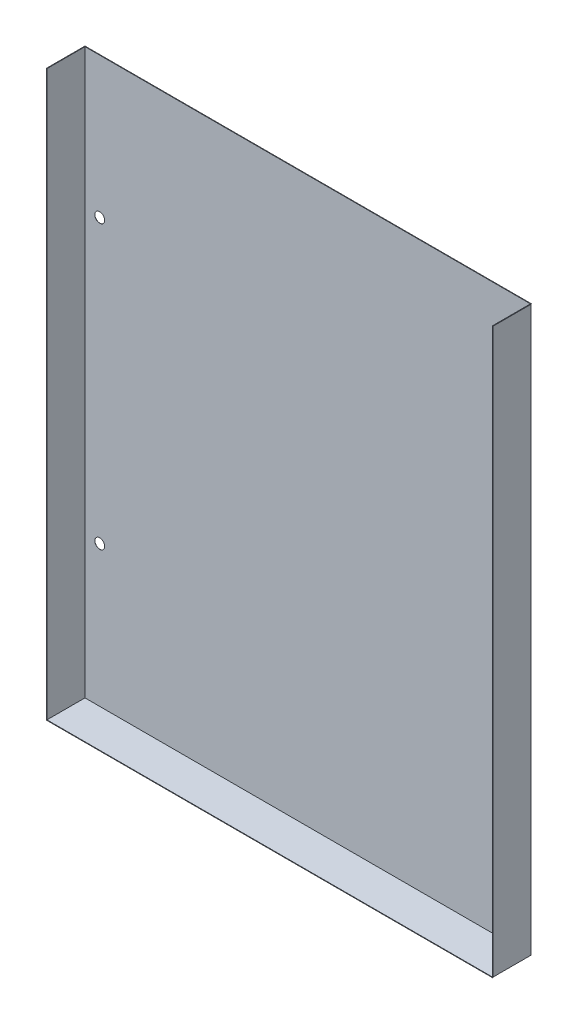
SolidWorks part; units mm, degrees
material "Kapton Film"
ref_plane "Front Plane" through (0, 0, 0) normal (0, 0, 1) x (1, 0, 0)
ref_plane "Top Plane" through (0, 0, 0) normal (0, 1, 0) x (1, 0, 0)
ref_plane "Right Plane" through (0, 0, 0) normal (1, 0, 0) x (0, 0, -1)
sketch "Sketch1" plane through (0, 0, 0) normal (0, 0, 1) x (1, 0, 0)
  line L0 (-83.72, 56.9443) -> (-83.72, -56.7081) construction
  line L1 (-89.6514, -113.4657) -> (89.6514, -113.4657)
  line L2 (-89.6514, -113.4657) -> (-89.6514, 113.4657)
  line L3 (-89.6514, 113.4657) -> (89.6514, 113.4657)
  line L4 (89.6514, -113.4657) -> (89.6514, 113.4657) construction
  line L5 (0, 113.4657) -> (0, -113.4657)
  circle A0 centre (-83.72, 56.9443) radius 2
  circle A1 centre (-83.72, -56.7081) radius 2
  dimension "D3" = 4
  dimension "D4" = 4
  dimension "D1" = 179.3028
  dimension "D2" = 226.9314
  dimension "D5" = 5.9314
  dimension "D6" = 56.7576
  dimension "D7" = 170.41
extrude "Heat Exchanger" add sketch "Sketch1" along normal blind 0.0686 contours L5 L3 L2 L1 region at (-44.7776, -0.0001, 0)
sketch "Sketch3" plane through (0, 0, 0) normal (0, 0, 1) x (1, 0, 0)
  line L3 (0, -113.5343) -> (0, -113.4657)
  line L4 (0, -113.4657) -> (-89.6514, -113.4657)
  line L5 (-89.72, -113.5343) -> (0, -113.5343)
  line L6 (-89.72, 113.4657) -> (-89.72, -113.5343)
  line L7 (-89.72, -113.5343) -> (0, -113.5343)
  line L8 (-89.72, 113.4657) -> (-89.72, -113.5343)
  line L9 (-89.6514, -113.4657) -> (-89.6514, 113.4657)
  line L10 (-89.6514, 113.4657) -> (-89.72, 113.4657)
  dimension "D1" = 0.0686
extrude "Convection Fins" add sketch "Sketch3" along normal blind 15.2969
sketch "Sketch5" plane through (0, 113.4657, 0) normal (0, 1, 0) x (1, 0, 0)
  line L2 (-89.8724, -15.2969) -> (-89.6514, -15.2969)
  line L3 (-89.6514, -15.2969) -> (-89.6514, -0.0686)
  line L4 (-89.8724, 0.1524) -> (0, 0.1524)
  line L5 (-89.8724, -15.2969) -> (-89.8724, 0.1524)
  line L6 (-89.8724, 0.1524) -> (0, 0.1524)
  line L7 (-89.8724, -15.2969) -> (-89.8724, 0.1524)
  line L8 (-89.6514, -0.0686) -> (0, -0.0686)
  line L9 (0, -0.0686) -> (0, 0.1524)
  dimension "D1" = 0.221
extrude "Top Overwrap" add sketch "Sketch5" along normal blind 0.0686
sketch "Sketch7" plane through (0, 0, 15.2969) normal (0, 0, 1) x (1, 0, 0)
  line L3 (-89.8724, 113.5343) -> (-89.6514, 113.5343)
  line L4 (-89.6514, 113.5343) -> (-89.6514, -113.4657)
  line L5 (0, -113.6867) -> (-89.8724, -113.6867)
  line L6 (-89.8724, -113.6867) -> (-89.8724, 113.5343)
  line L7 (0, -113.6867) -> (-89.8724, -113.6867)
  line L8 (-89.8724, -113.6867) -> (-89.8724, 113.5343)
  line L9 (-89.6514, -113.4657) -> (0, -113.4657)
  line L10 (0, -113.4657) -> (0, -113.6867)
  dimension "D1" = 0.221
extrude "Side Overwrap" add sketch "Sketch7" along normal blind 0.0686
mirror "Mirror1" about plane through (0, 0, 0) normal (1, 0, 0) of "Heat Exchanger", "Side Overwrap", "Top Overwrap", "Convection Fins"
